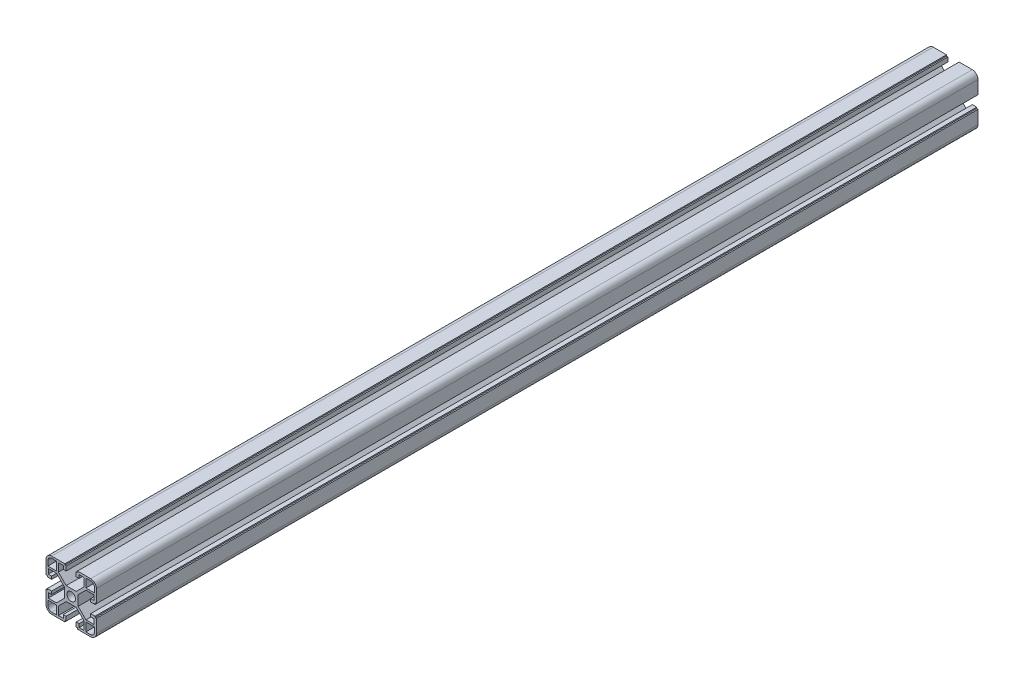
SolidWorks part; units mm, degrees
material "6061-T6 (SS)"
ref_plane "Front Plane" through (0, 0, 0) normal (0, 0, 1) x (1, 0, 0)
ref_plane "Top Plane" through (0, 0, 0) normal (0, 1, 0) x (1, 0, 0)
ref_plane "Right Plane" through (0, 0, 0) normal (1, 0, 0) x (0, 0, -1)
sketch "Sketch1" plane through (0, 0, 0) normal (0, 0, 1) x (1, 0, 0)
  line L0 (3.4, 0) -> (5.5, 0)
  line L1 (10.19, 11.69) -> (4, 5.5)
  line L2 (11.69, 10.19) -> (5.5, 4)
  line L3 (18.2, 10.19) -> (11.69, 10.19)
  line L4 (18.2, 10.19) -> (18.2, 6.3)
  line L5 (18.2, 6.3) -> (15.5, 6.3)
  line L6 (15.5, 6.3) -> (15.5, 4)
  line L7 (15.5, 4) -> (19, 4)
  line L8 (19, 4) -> (19, 5)
  line L9 (19, 5) -> (20, 5)
  line L10 (20, 5) -> (20, 15.5)
  line L11 (15.5, 20) -> (5, 20)
  line L12 (18.5, 11.69) -> (18.5, 15.5)
  line L13 (15.5, 18.5) -> (11.69, 18.5)
  line L14 (11.69, 11.69) -> (11.69, 18.5)
  line L15 (0, 3.4) -> (0, 5.5)
  line L16 (4, 5.5) -> (0, 5.5)
  line L17 (5, 20) -> (5, 19)
  line L18 (5.5, 0) -> (5.5, 4)
  line L19 (5, 19) -> (4, 19)
  line L20 (4, 19) -> (4, 15.5)
  line L21 (4, 15.5) -> (6.3, 15.5)
  line L22 (10.19, 11.69) -> (10.19, 18.2)
  line L23 (11.69, 11.69) -> (18.5, 11.69)
  line L24 (6.3, 18.2) -> (6.3, 15.5)
  line L25 (10.19, 18.2) -> (6.3, 18.2)
  arc A0 (20, 15.5) -> (15.5, 20) centre (15.5, 15.5) ccw
  arc A1 (18.5, 15.5) -> (15.5, 18.5) centre (15.5, 15.5) ccw
  arc A2 (3.4, 0) -> (0, 3.4) centre (0, 0) ccw
  point P4 (0, 4.45)
  dimension "D3" = 4.5
  dimension "D18" = 1.5
  dimension "D9" = 3.4
  dimension "D20" = 1.8
  dimension "D25" = 3
  dimension "D1" = 5.5
  dimension "D2" = 1.5
  dimension "D4" = 14.5
  dimension "D5" = 1.5
  dimension "D6" = 2.1
  dimension "D7" = 2.3
  dimension "D8" = 1.8
  dimension "D10" = 6.81
  dimension "D11" = 2.1
  dimension "D12" = 1
  dimension "D13" = 4.5
  dimension "D14" = 45
  dimension "D15" = 14.5
  dimension "D16" = 1
  dimension "D17" = 1.5
  dimension "D19" = 6.81
  dimension "D21" = 4.5
  dimension "D22" = 2.3
  dimension "D23" = 1
  dimension "D24" = 1
  dimension "D26" = 8.754
  dimension "D27" = 8.754
  dimension "D28" = 4
  dimension "D29" = 4
extrude "Boss-Extrude1" add sketch "Sketch1" along normal blind 700
mirror "Mirror1" about plane through (0, 0, 0) normal (0, 1, 0) of "Boss-Extrude1"
mirror "Mirror2" about plane through (0, 0, 0) normal (1, 0, 0) of "Boss-Extrude1"
mirror "Mirror3" about plane through (0, 0, 0) normal (0, 1, 0) of "Mirror2"
